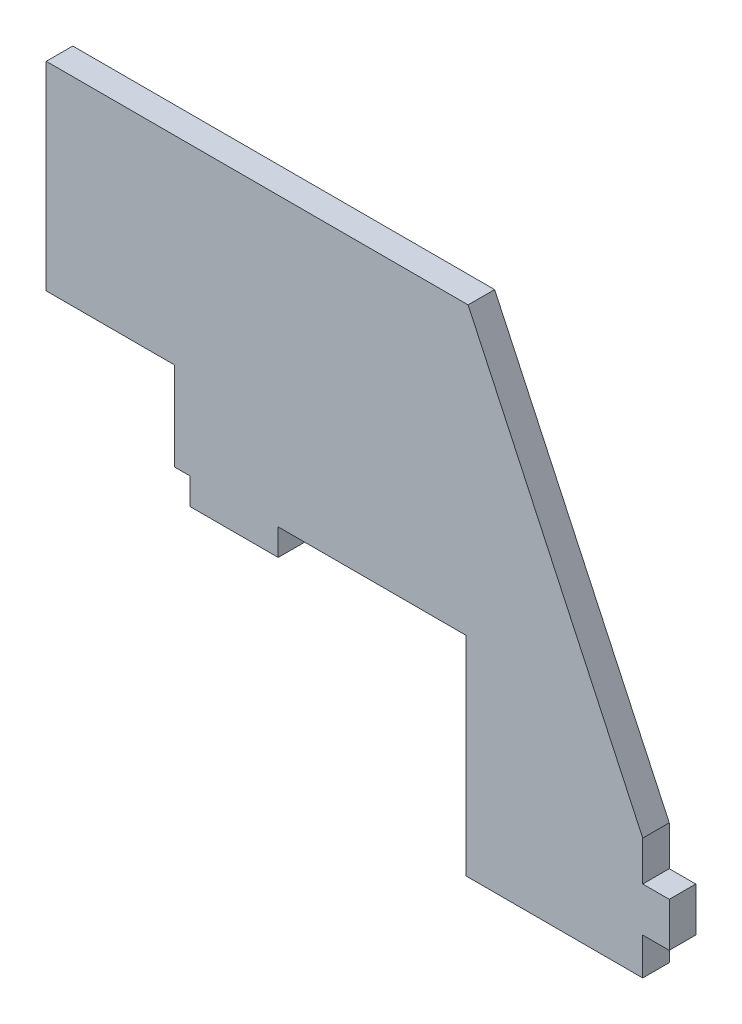
SolidWorks part; units mm, degrees
ref_plane "Plan de face" through (0, 0, 0) normal (0, 0, 1) x (1, 0, 0)
ref_plane "Plan de dessus" through (0, 0, 0) normal (0, 1, 0) x (1, 0, 0)
ref_plane "Plan de droite" through (0, 0, 0) normal (1, 0, 0) x (0, 0, -1)
sketch "Esquisse1" plane through (0, 0, 0) normal (0, 0, 1) x (1, 0, 0)
  line L1 (-67.5, 56.085) -> (67.5, 56.085)
  line L2 (-67.5, 56.085) -> (-67.5, -56.085)
  line L3 (-67.5, -56.085) -> (67.5, -56.085)
  line L4 (67.5, 56.085) -> (67.5, -56.085)
  dimension "D1" = 135
  dimension "D2" = 112.17
  dimension "D3" = 67.5
  dimension "D4" = 56.085
extrude "Boss.-Extru.1" add sketch "Esquisse1" along normal blind 6
sketch "Esquisse2" plane through (0, 0, 6) normal (0, 0, 1) x (1, 0, 0)
  line L0 (-67.5, -56.085) -> (67.5, -56.085) construction
  line L1 (27.5, -56.085) -> (-67.5, -56.085)
  line L2 (27.5, -56.085) -> (27.5, -8.915)
  line L3 (-38.5, -8.915) -> (27.5, -8.915)
  line L4 (-67.5, -56.085) -> (-67.5, -8.915)
  line L5 (-67.5, 56.085) -> (-67.5, -56.085) construction
  line L6 (-67.5, -8.915) -> (-67.5, 11.085)
  line L7 (67.5, -28.665) -> (27.9804, 56.085)
  line L9 (67.5, -56.085) -> (67.5, 56.085) construction
  line L10 (67.5, 56.085) -> (-67.5, 56.085) construction
  line L11 (27.9804, 56.085) -> (67.5, 56.085)
  line L12 (67.5, 56.085) -> (67.5, -28.665)
  line L14 (-67.5, 11.085) -> (-38.5, 11.085)
  line L15 (-38.5, -8.915) -> (-38.5, 11.085)
  dimension "D1" = 47.17
  dimension "D2" = 95
  dimension "D3" = 27.42
  dimension "D4" = 155
  dimension "D5" = 115
  dimension "D6" = 29
  dimension "D7" = 20
extrude "Enlèv. mat.-Extru.1" cut sketch "Esquisse2" against normal blind 6
sketch "Esquisse3" plane through (0, 0, 6) normal (0, 0, 1) x (1, 0, 0)
  line L0 (67.5, -56.085) -> (67.5, -28.665) construction
  line L1 (67.5, -47.665) -> (73.5, -47.665)
  line L2 (67.5, -47.665) -> (67.5, -37.665)
  line L3 (67.5, -37.665) -> (73.5, -37.665)
  line L4 (73.5, -47.665) -> (73.5, -37.665)
  line L6 (-35, -8.915) -> (-15, -8.915)
  line L7 (-35, -8.915) -> (-35, -14.915)
  line L8 (-35, -14.915) -> (-15, -14.915)
  line L9 (-15, -8.915) -> (-15, -14.915)
  line L10 (27.5, -8.915) -> (-38.5, -8.915) construction
  line L16 (27.5, -56.085) -> (27.5, -8.915) construction
  line L17 (27.5, -56.085) -> (67.5, -56.085) construction
  dimension "D3" = 6
  dimension "D4" = 20
  dimension "D5" = 42.5
  dimension "D6" = 10
  dimension "D7" = 6
  dimension "D8" = 8.42
extrude "Boss.-Extru.2" add sketch "Esquisse3" against normal blind 6
equation "\"D3@Esquisse1\"=\"D1@Esquisse1\"/2"
equation "\"D4@Esquisse1\"=\"D2@Esquisse1\"/2"
